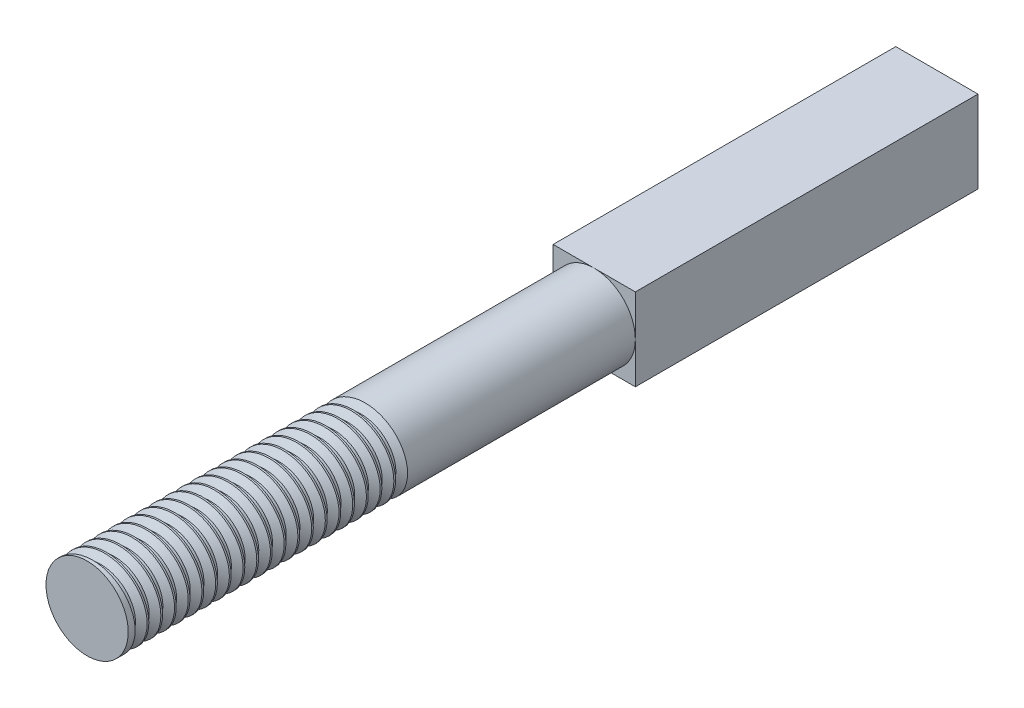
SolidWorks part; units mm, degrees
ref_plane "Front Plane" through (0, 0, 0) normal (0, 0, 1) x (1, 0, 0)
ref_plane "Top Plane" through (0, 0, 0) normal (0, 1, 0) x (1, 0, 0)
ref_plane "Right Plane" through (0, 0, 0) normal (1, 0, 0) x (0, 0, -1)
sketch "Sketch4" plane through (0, 0, 0) normal (0, 0, 1) x (1, 0, 0)
  line L1 (-3, 3) -> (3, 3)
  line L2 (-3, 3) -> (-3, -3)
  line L3 (-3, -3) -> (3, -3)
  line L4 (3, 3) -> (3, -3)
  line L5 (-3, 3) -> (3, -3) construction
  line L6 (-3, -3) -> (3, 3) construction
  point P0 (0, 0)
  dimension "D1" = 6
  dimension "D2" = 6
extrude "Boss-Extrude3" add sketch "Sketch4" along normal blind 25
sketch "Sketch5" plane through (0, 0, 25) normal (0, 0, 1) x (1, 0, 0)
  circle A0 centre (0, 0) radius 3
extrude "Boss-Extrude4" add sketch "Sketch5" along normal blind 17
sketch "Sketch6" plane through (0, 0, 42) normal (0, 0, 1) x (1, 0, 0)
  circle A0 centre (0, 0) radius 3
extrude "Boss-Extrude5" add sketch "Sketch6" along normal blind 20
thread "Thread1" pitch 1 method cut profile "Thread Profile1" start angle 0, offset 0, length 20, pitch 1, diameter 6
ref_plane "Plane1" through (-3, 0, 62) normal (0, -1, 0) x (-1, 0, 0)
sketch "Thread Profile1" plane through (-3, 0, 62) normal (0, -1, 0) x (-1, 0, 0)
  line L0 (0, 0) -> (0, 1) construction
  line L11 (0, 0) -> (0, 0.875)
  line L12 (0, 0.875) -> (-0.5413, 0.5625)
  line L13 (-0.5413, 0.5625) -> (-0.5413, 0.3125)
  line L15 (-0.5413, 0.3125) -> (0, 0)
  line L17 (-0.5413, 0.4375) -> (0, 0.4375) construction
  point P2 (0, 0)
  dimension "Pitch" = 1
  dimension "Profile_Angle" = 60
  dimension "Profile_Land" = 0.25
  dimension "Profile_Height" = 0.5413
ref_plane "Plane2" through (0, 0, 0) normal (1, 0, 0) x (0, 0, -1)
sketch "Sketch7" plane through (0, 0, 0) normal (1, 0, 0) x (0, 0, -1)
  line L0 (-63.2995, 0) -> (5.0206, 0) construction
